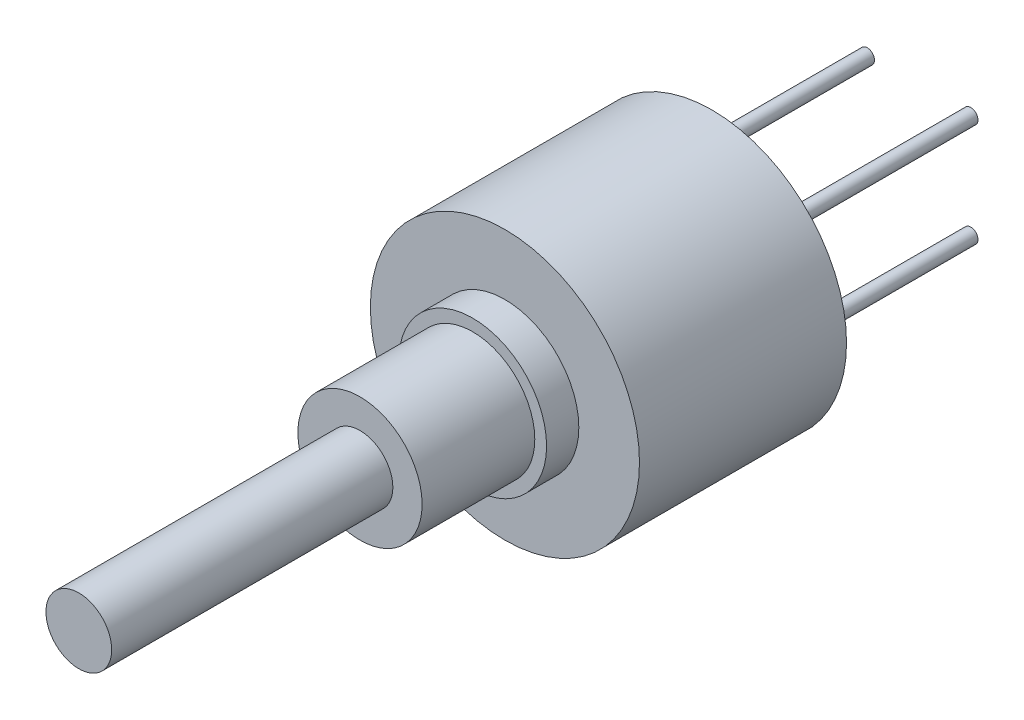
SolidWorks part; units mm, degrees
material "1060 Alloy"
ref_plane "Front Plane" through (0, 0, 0) normal (0, 0, 1) x (1, 0, 0)
ref_plane "Top Plane" through (0, 0, 0) normal (0, 1, 0) x (1, 0, 0)
ref_plane "Right Plane" through (0, 0, 0) normal (1, 0, 0) x (0, 0, -1)
sketch "Sketch1" plane through (0, 0, 0) normal (0, 0, 1) x (1, 0, 0)
  circle A0 centre (0, 0) radius 6.5
  circle A1 centre (0, 0) radius 3.57
  circle A2 centre (0, 0) radius 3
  circle A3 centre (0, 0) radius 1.5875
extrude "Boss-Extrude1" add sketch "Sketch1" along normal blind 10 contours A0 A1 | A1 A2 | A2 A3 | A3 region at (-6.3162, 0, 0) region at (-3.469, 0, 0) region at (-2.9151, 0, 0) region at (0, 0, 0)
extrude "Boss-Extrude2" add sketch "Sketch1<3>" along normal blind 11.557 contours A3 | A2 A3 | A1 A2 region at (-3.469, 0, 0) region at (-2.9151, 0, 0) region at (0, 0, 0)
sketch "Sketch1<3>" plane through (0, 0, 0) normal (0, 0, 1) x (1, 0, 0) same geometry as "Sketch1"
extrude "Boss-Extrude3" add sketch "Sketch1<4>" along normal blind 17 contours A3 | A2 A3 region at (-2.9151, 0, 0) region at (0, 0, 0)
sketch "Sketch1<4>" plane through (0, 0, 0) normal (0, 0, 1) x (1, 0, 0) same geometry as "Sketch1"
extrude "Boss-Extrude4" add sketch "Sketch1<5>" along normal blind 30.5816 contours A3 region at (0, 0, 0)
sketch "Sketch1<5>" plane through (0, 0, 0) normal (0, 0, 1) x (1, 0, 0) same geometry as "Sketch1"
sketch "Sketch2" plane through (0, 0, 0) normal (0, 0, -1) x (-1, 0, 0)
  line L0 (0, 0) -> (0, 2.5) construction
  line L1 (0, 2.5) -> (2.5, 2.5) construction
  line L2 (2.5, 2.5) -> (2.5, -2.5) construction
  line L3 (2.5, -2.5) -> (-2.5, -2.5) construction
  line L4 (-2.5, -2.5) -> (-2.5, 2.5) construction
  line L5 (-2.5, 2.5) -> (0, 2.5) construction
  circle A0 centre (-2.5, 2.5) radius 0.35
  circle A1 centre (2.5, 2.5) radius 0.35
  circle A2 centre (2.5, -2.5) radius 0.35
  circle A3 centre (-2.5, -2.5) radius 0.35
extrude "Boss-Extrude5" add sketch "Sketch2" along normal blind 10
